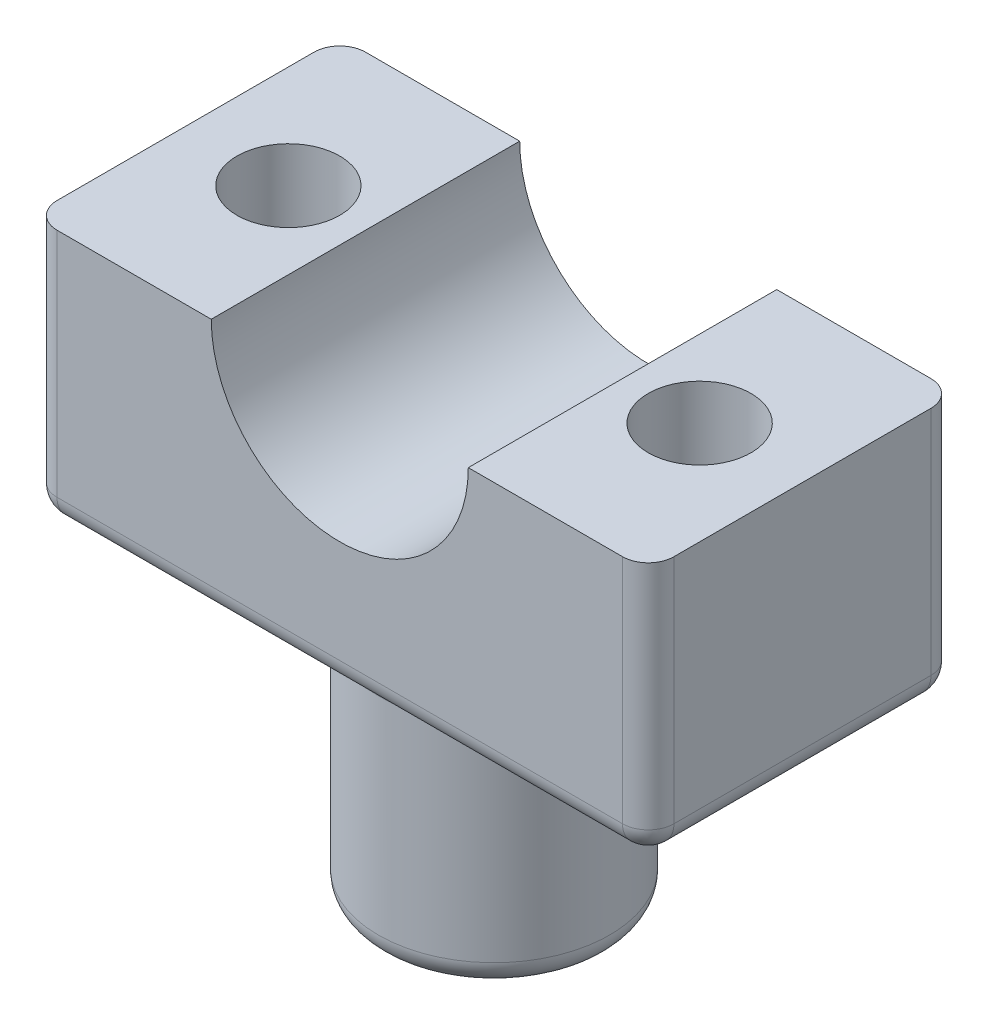
SolidWorks part; units mm, degrees
ref_plane "Front Plane" through (0, 0, 0) normal (0, 0, 1) x (1, 0, 0)
ref_plane "Top Plane" through (0, 0, 0) normal (0, 1, 0) x (1, 0, 0)
ref_plane "Right Plane" through (0, 0, 0) normal (1, 0, 0) x (0, 0, -1)
sketch "Sketch1" plane through (0, 0, 0) normal (0, 1, 0) x (1, 0, 0)
  line L1 (-11, -6) -> (11, -6)
  line L2 (-12, -5) -> (-12, 5)
  line L3 (-11, 6) -> (11, 6)
  line L4 (12, -5) -> (12, 5)
  arc A0 (-11, -6) -> (-12, -5) centre (-11, -5) cw
  arc A1 (11, -6) -> (12, -5) centre (11, -5) ccw
  arc A2 (11, 6) -> (12, 5) centre (11, 5) cw
  arc A3 (-12, 5) -> (-11, 6) centre (-11, 5) cw
  circle A4 centre (0, 0) radius 4.5
  circle A6 centre (8, 0) radius 2
  circle A7 centre (-8, 0) radius 2
  point P19 (0, 0)
  point P20 (0, 0)
  dimension "D1" = 1
extrude "Boss-Extrude1" add sketch "Sketch1" along normal blind 10 contours A3 L2 A0 L1 A1 L4 A2 L3 A7 A6 A4 | A4 region at (-11.5174, 0, 5.5174) region at (0, 0, 0)
extrude "Boss-Extrude2" add sketch "Sketch1<3>" against normal blind 10 contours A4 region at (0, 0, 0)
sketch "Sketch1<3>" plane through (0, 0, 0) normal (0, 1, 0) x (1, 0, 0) same geometry as "Sketch1"
sketch "Sketch2" plane through (0, 0, 6) normal (0, 0, 1) x (1, 0, 0)
  line L0 (-11, 10) -> (11, 10) construction
  line L1 (-5, 10) -> (5, 10)
  arc A0 (-5, 10) -> (5, 10) centre (0, 10) ccw
extrude "Cut-Extrude1" cut sketch "Sketch2" against normal through all
fillet "Fillet1" radius 1 9 edges at (-11.7071, 0, 5.7071) (-12, 0, 0) (-11.7071, 0, -5.7071) (0, 0, -6) (11.7071, 0, -5.7071) (12, 0, 0) (11.7071, 0, 5.7071) (0, -10, 4.5) (0, 0, 6)
fillet "Fillet2" radius 1 1 edges at (0, 0, 4.5)
sketch "Sketch3" plane through (0, -10, 0) normal (0, -1, 0) x (1, 0, 0)
  circle A0 centre (0, 0) radius 2.5
extrude "Cut-Extrude2" cut sketch "Sketch3" against normal blind 10
cosmetic thread "Cosmetic Thread1" parameters "D1"=10, "D2"=6
